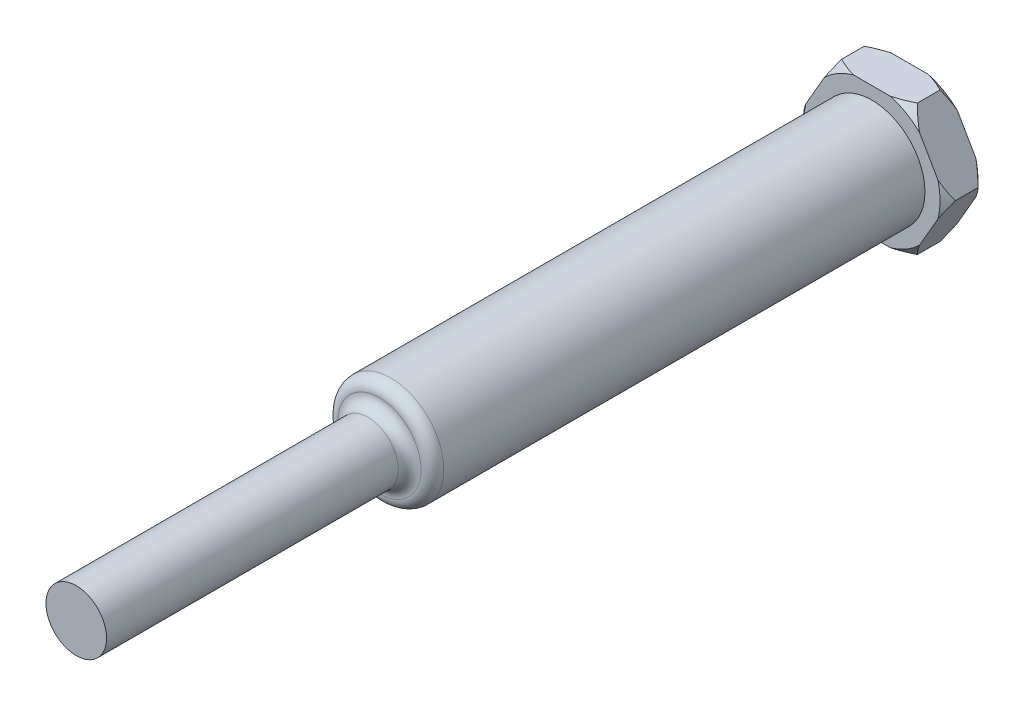
SolidWorks part; units mm, degrees
material "Alumina"
ref_plane "Front Plane" through (0, 0, 0) normal (0, 0, 1) x (1, 0, 0)
ref_plane "Top Plane" through (0, 0, 0) normal (0, 1, 0) x (1, 0, 0)
ref_plane "Right Plane" through (0, 0, 0) normal (1, 0, 0) x (0, 0, -1)
sketch "Sketch1" plane through (0, 0, 0) normal (0, 0, 1) x (1, 0, 0)
  line L0 (0, 0) -> (0, -6.9701) construction
  line L1 (5, 8.6603) -> (-5, 8.6603)
  line L2 (-5, 8.6603) -> (-10, 0)
  line L3 (-10, 0) -> (-5, -8.6603)
  line L4 (-5, -8.6603) -> (5, -8.6603)
  line L5 (5, -8.6603) -> (10, 0)
  line L6 (10, 0) -> (5, 8.6603)
  circle A0 centre (0, 0) radius 10
  circle A1 centre (0, 0) radius 8.6603 construction
  dimension "D1" = 20
extrude "Boss-Extrude1" add sketch "Sketch1" along normal blind 5 contours L5 L6 L1 L2 L3 L4 region at (0, 0, 0)
sketch "Sketch2" plane through (0, 0, 5) normal (0, 0, 1) x (1, 0, 0)
  circle A0 centre (0, 0) radius 7
  dimension "D1" = 14
extrude "Boss-Extrude2" add sketch "Sketch2" along normal blind 65
sketch "Sketch3" plane through (0, 0, 70) normal (0, 0, 1) x (1, 0, 0)
  circle A0 centre (0, 0) radius 4
  dimension "D1" = 8
extrude "Boss-Extrude3" add sketch "Sketch3" along normal blind 40
fillet "Fillet1" radius 1.5 2 edges at (4, 0, 70) (7, 0, 70)
sketch "Sketch5" plane through (0, 0, 0) normal (0, 1, 0) x (1, 0, 0)
  line L0 (-10, -1) -> (-9, 0)
  line L1 (-9, 0) -> (-10, 0)
  line L2 (-10, 0) -> (-10, -1)
  line L3 (-10, -4) -> (-9, -5)
  line L4 (-9, -5) -> (-10, -5)
  line L5 (-10, -5) -> (-10, -4)
  line L6 (5, -5) -> (-5, -5) construction
  line L7 (0, 0) -> (0, -5.5889) construction
  dimension "D1" = 45
  dimension "D2" = 1
  dimension "D3" = 10
  dimension "D4" = 0
  dimension "D5" = 1
  dimension "D6" = 45
  dimension "D7" = 10
  dimension "D8" = 0
revolve "Cut-Revolve1" cut sketch "Sketch5" angle 360 about L7
